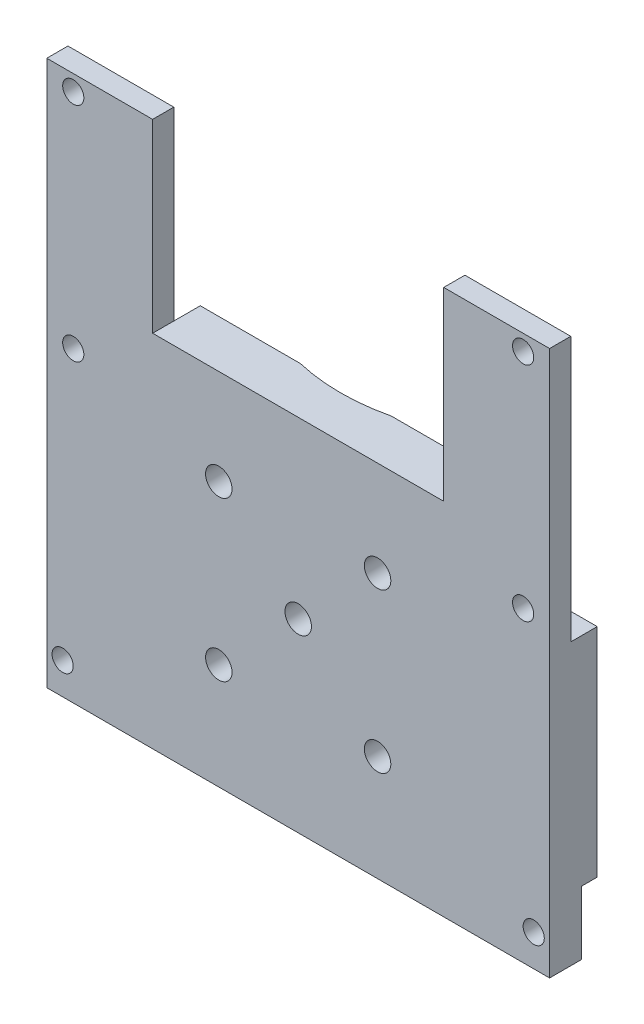
SolidWorks part; units mm, degrees
ref_plane "Front Plane" through (0, 0, 0) normal (0, 0, 1) x (1, 0, 0)
ref_plane "Top Plane" through (0, 0, 0) normal (0, 1, 0) x (1, 0, 0)
ref_plane "Right Plane" through (0, 0, 0) normal (1, 0, 0) x (0, 0, -1)
sketch "Sketch1" plane through (0, 0, 0) normal (0, 1, 0) x (1, 0, 0)
  circle A0 centre (0, 0) radius 37.5
  dimension "D1" = 75
extrude "Boss-Extrude1" add sketch "Sketch1" along normal blind 12
sketch "Sketch2" plane through (0, 12, 0) normal (0, 1, 0) x (1, 0, 0)
  circle A0 centre (0, 0) radius 30
  dimension "D1" = 60
extrude "Boss-Extrude2" add sketch "Sketch2" along normal blind 56
ref_plane "Plane1" through (0, 0, 37.5) normal (0, 0, 1) x (1, 0, 0)
sketch "Sketch4" plane through (0, 0, 37.5) normal (0, 0, 1) x (1, 0, 0)
  line L1 (37.5, 83) -> (-37.5, 83)
  line L2 (30, 68) -> (-30, 68)
  line L3 (37.5, 68) -> (-37.5, 68)
  line L4 (-37.5, 83) -> (-37.5, 68)
  line L5 (37.5, 83) -> (37.5, 68)
  line L6 (-37.5, 12) -> (-37.5, 0) construction
  line L7 (0, 68) -> (0, 76) construction
  circle A0 centre (0, 76) radius 3.5
  dimension "D4" = 7
  dimension "D2" = 75
  dimension "D5" = 8
  dimension "D1" = 0
  dimension "D3" = 15
extrude "Boss-Extrude3" add sketch "Sketch4" along normal blind 5 and the other way blind 1 separate body
other "Move Face3" face at (-37.5, 75.5, 39.5) face at (37.5, 75.5, 39.5) offset 10 parameters "D1"=10
sketch "Sketch6" plane through (0, 0, 0) normal (0, -1, 0) x (1, 0, 0)
  line L0 (0, 0) -> (0, -42.5) construction
  line L1 (-37.5, 0) -> (-42.5, 0) construction
  line L2 (37.5, 0) -> (42.5, 0) construction
  line L3 (0, 0) -> (-37.5, 0) construction
  line L4 (0, 0) -> (37.5, 0) construction
  line L5 (42.5, 0) -> (37.5, 0)
  line L6 (-37.5, 0) -> (-42.5, 0)
  circle A2 centre (0, 0) radius 42.5
  arc A3 (42.5, 0) -> (-42.5, 0) centre (0, 0) ccw
  arc A4 (0, -37.5) -> (37.5, 0) centre (0, 0) ccw construction
  circle A5 centre (0, 0) radius 37.5
  arc A6 (37.5, 0) -> (-37.5, 0) centre (0, 0) ccw
  arc A7 (0, -42.5) -> (42.5, 0) centre (0, 0) ccw construction
  arc A8 (-37.5, 0) -> (0, -37.5) centre (0, 0) ccw construction
  arc A9 (-42.5, 0) -> (0, -42.5) centre (0, 0) ccw construction
  circle A13 centre (0, 0) radius 42.5 construction
  circle A15 centre (0, 0) radius 42.5 construction
  dimension "D3" = 90
  dimension "D4" = 90
  dimension "D1" = 5
  dimension "D2" = 0
extrude "Boss-Extrude4" add sketch "Sketch6" against normal up to surface (12 mm away) separate body up to face at (0, 12, 30)
delete or keep bodies "Body-Delete/Keep 1" type delete bodies bodies 102
sketch "Sketch7" plane through (0, 68, 0) normal (0, -1, 0) x (1, 0, 0)
  line L9 (-8.6023, 36.5) -> (8.6023, 36.5) construction
  line L10 (8.6023, 36.5) -> (47.5, 36.5)
  line L17 (47.5, 36.5) -> (47.5, 42.5)
  line L18 (47.5, 42.5) -> (-47.5, 42.5)
  line L19 (-47.5, 42.5) -> (-47.5, 36.5)
  line L20 (-47.5, 36.5) -> (47.5, 36.5)
  line L21 (47.5, 36.5) -> (47.5, 42.5)
  line L22 (47.5, 42.5) -> (-47.5, 42.5)
  line L23 (-47.5, 42.5) -> (-47.5, 36.5)
  line L24 (-47.5, 36.5) -> (-8.6023, 36.5)
  arc A2 (-8.6023, 36.5) -> (-37.5, 0) centre (0, 0) ccw construction
  arc A4 (37.5, 0) -> (-37.5, 0) centre (0, 0) ccw
  arc A5 (8.6023, 36.5) -> (-8.6023, 36.5) centre (0, 0) ccw
  arc A6 (37.5, 0) -> (8.6023, 36.5) centre (0, 0) ccw construction
  dimension "D1" = 0
  dimension "D2" = 0
extrude "Boss-Extrude5" add sketch "Sketch7" along normal up to surface (68 mm away) up to face at (0, 0, 20)
other "Move Face1" face at (0, 41.5, 42.5) offset 10 parameters "D1"=10
sketch "Sketch11" plane through (0, 0, 0) normal (0, -1, 0) x (1, 0, 0)
  line L1 (-47.5, 37.5) -> (47.5, 37.5)
  line L2 (-21.7715, 36.5) -> (-8.6023, 36.5)
  line L3 (-21.7715, 36.5) -> (-8.6023, 36.5) construction
  line L4 (-21.7715, 37.5) -> (-8.6023, 37.5) construction
  line L5 (47.5, 36.5) -> (47.5, 52.5) construction
  line L6 (47.5, 37.5) -> (47.5, 52.5)
  line L7 (47.5, 52.5) -> (-47.5, 52.5)
  line L8 (-47.5, 52.5) -> (-47.5, 37.5)
  dimension "D1" = 0
  dimension "D2" = 1
extrude "Boss-Extrude7" add sketch "Sketch11" along normal blind 20
sketch "Sketch12" plane through (0, 0, 37.5) normal (0, 0, -1) x (-1, 0, 0)
  line L0 (0, 0) -> (0, 35)
  line L3 (15, 20) -> (-15, 20) construction
  line L4 (15, 20) -> (15, 50) construction
  line L5 (15, 50) -> (-15, 50) construction
  line L6 (-15, 20) -> (-15, 50) construction
  line L7 (15, 20) -> (-15, 50) construction
  line L8 (15, 50) -> (-15, 20) construction
  circle A0 centre (0, 35) radius 25 construction
  circle A2 centre (-15, 50) radius 2.5
  circle A3 centre (15, 50) radius 2.5
  circle A4 centre (15, 20) radius 2.5
  circle A5 centre (-15, 20) radius 2.5
  dimension "D1" = 50
  dimension "D4" = 30
  dimension "D5" = 5
  dimension "D2" = 35
  dimension "D3" = 30
extrude "Cut-Extrude1" cut sketch "Sketch12" against normal through all both and the other way through all contours A5 | A4 | A2 | A3 region at (-15, 20, 37.5) region at (15, 20, 37.5)
sketch "Sketch13" plane through (0, 0, 36.5) normal (0, 0, -1) x (-1, 0, 0)
  circle A2 centre (-15, 50) radius 6.5
  circle A3 centre (-15, 50) radius 6.5
  circle A5 centre (15, 50) radius 6.5
  circle A6 centre (15, 50) radius 6.5
  circle A9 centre (-15, 20) radius 6.5
  circle A12 centre (15, 20) radius 6.5
  dimension "D1" = 4
  dimension "D2" = 4
extrude "Cut-Extrude2" cut sketch "Sketch13" against normal blind 5
other "Move Face2" flip direction yes face at (-17.5, 20, 52.5) offset 7 parameters "D1"=7
other "DeleteFace1" face at (0, -8, 37.5) face at (0, -20, 41.5) and patch yes
sketch "Sketch14" plane through (0, 0, 36.5) normal (0, 0, -1) x (-1, 0, 0)
  line L2 (47.5, 0) -> (-42.5, 0)
  line L16 (-42.5, 12) -> (47.5, 12)
  line L17 (47.5, 83) -> (47.5, 0) construction
  line L18 (47.5, 12) -> (47.5, 0)
  line L19 (-42.5, 0) -> (-47.5, 0)
  line L20 (-47.5, 0) -> (-47.5, 12)
  line L21 (-47.5, 0) -> (-47.5, 83) construction
  line L22 (-47.5, 12) -> (-42.5, 12)
extrude "Cut-Extrude3" cut sketch "Sketch14" against normal blind 3 and the other way through all
sketch "Sketch15" plane through (0, 0, 39.5) normal (0, 0, -1) x (-1, 0, 0)
  line L0 (0, 0) -> (0, 12) construction
  line L1 (47.5, 0) -> (47.5, 12) construction
  line L2 (-44.5, 6) -> (44.5, 6) construction
  line L3 (47.5, 12) -> (-47.5, 12) construction
  circle A0 centre (44.5, 6) radius 2
  circle A1 centre (-44.5, 6) radius 2
  point P8 (0, 6)
  dimension "D2" = 4
  dimension "D1" = 3
extrude "Cut-Extrude4" cut sketch "Sketch15" against normal through all
other "Move Face4" face at (0, 83, 41) offset 20 parameters "D1"=20
sketch "Sketch16" plane through (0, 0, 36.5) normal (0, 0, -1) x (-1, 0, 0)
  line L0 (-27.5, 103) -> (-27.5, 68)
  line L1 (-47.5, 103) -> (47.5, 103) construction
  line L2 (-27.5, 68) -> (27.5, 68)
  line L3 (27.5, 68) -> (27.5, 103)
  line L4 (47.5, 103) -> (47.5, 12) construction
  line L5 (-47.5, 12) -> (-47.5, 103) construction
  line L6 (-27.5, 103) -> (27.5, 103)
  dimension "D1" = 20
  dimension "D2" = 20
  dimension "D3" = 35
extrude "Cut-Extrude5" cut sketch "Sketch16" against normal blind 10
sketch "Sketch17" plane through (0, 0, 36.5) normal (0, 0, -1) x (-1, 0, 0)
  line L0 (27.5, 103) -> (47.5, 103)
  line L1 (47.5, 103) -> (47.5, 53)
  line L2 (47.5, 103) -> (47.5, 12) construction
  line L3 (47.5, 53) -> (27.5, 53)
  line L4 (27.5, 53) -> (27.5, 103)
  line L5 (0, 25.025) -> (0, -25.025) construction
  line L6 (-47.5, 53) -> (-27.5, 53)
  line L7 (-47.5, 103) -> (-47.5, 53)
  line L8 (-27.5, 103) -> (-47.5, 103)
  line L9 (-27.5, 53) -> (-27.5, 103)
  dimension "D1" = 50
extrude "Cut-Extrude6" cut sketch "Sketch17" against normal blind 5
sketch "Sketch18" plane through (0, 0, 41.5) normal (0, 0, -1) x (-1, 0, 0)
  line L0 (-47.5, 53) -> (-27.5, 53) construction
  line L1 (-47.5, 103) -> (-47.5, 53) construction
  line L2 (-27.5, 103) -> (-47.5, 103) construction
  line L3 (0, 25.025) -> (0, -25.025) construction
  circle A0 centre (-42.5, 58) radius 2
  circle A1 centre (-42.5, 100) radius 2
  circle A2 centre (42.5, 100) radius 2
  circle A3 centre (42.5, 58) radius 2
  dimension "D2" = 5
  dimension "D3" = 4
  dimension "D4" = 4
  dimension "D5" = 5
  dimension "D6" = 3
  dimension "D1" = 5
extrude "Cut-Extrude7" cut sketch "Sketch18" against normal through all
sketch "Sketch19" plane through (0, 0, 45.5) normal (0, 0, 1) x (1, 0, 0)
  line L0 (-15, 50) -> (15, 20) construction
  line L1 (15, 50) -> (-15, 20) construction
  circle A0 centre (0, 35) radius 2.5
  dimension "D1" = 5
extrude "Cut-Extrude8" cut sketch "Sketch19" against normal through all
sketch "Sketch20" plane through (0, 0, 45.5) normal (0, 0, 1) x (1, 0, 0)
  line L0 (0, 35) -> (0, 6)
  line L1 (0, 6) -> (-44.5, 6)
